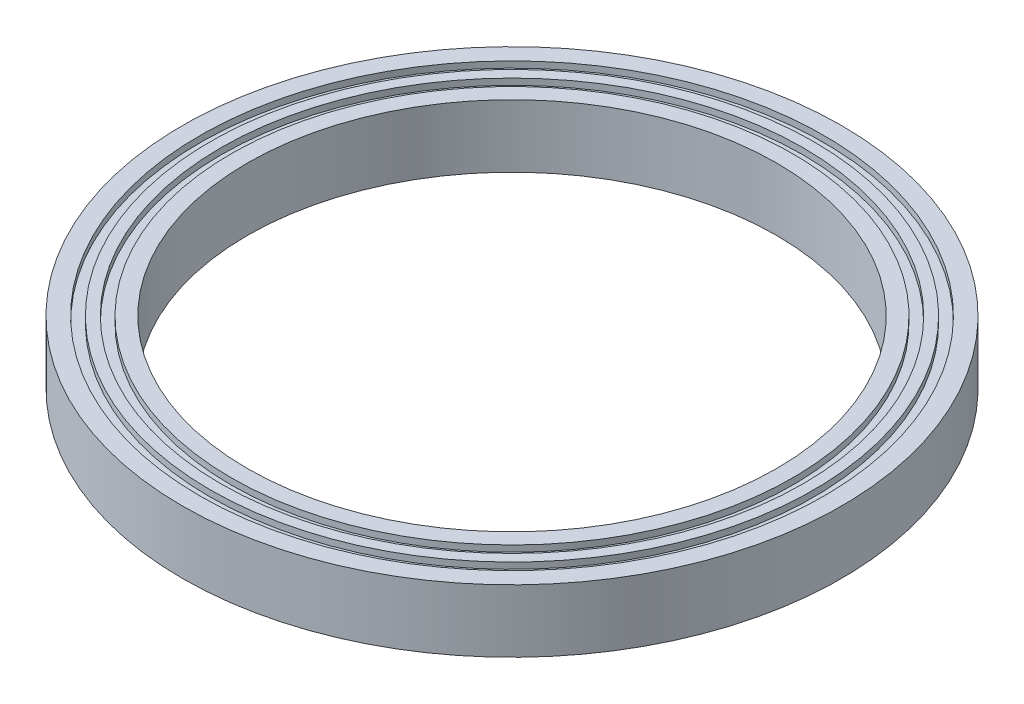
SolidWorks part; units mm, degrees
ref_plane "Front Plane" through (0, 0, 0) normal (0, 0, 1) x (1, 0, 0)
ref_plane "Top Plane" through (0, 0, 0) normal (0, 1, 0) x (1, 0, 0)
ref_plane "Right Plane" through (0, 0, 0) normal (1, 0, 0) x (0, 0, -1)
sketch "Sketch1" plane through (0, 0, 0) normal (0, 1, 0) x (1, 0, 0)
  circle A0 centre (0, 0) radius 9945
  circle A1 centre (0, 0) radius 8945
  dimension "D1" = 19890
  dimension "D2" = 17890
  dimension "D3" = 1000
extrude "Boss-Extrude1" add sketch "Sketch1" along normal blind 600
sketch "Sketch2" plane through (0, 0, 0) normal (0, 1, 0) x (1, 0, 0)
  circle A0 centre (0, 0) radius 8890
  circle A1 centre (0, 0) radius 9945
  dimension "D1" = 17780
  dimension "D2" = 19890
extrude "Boss-Extrude5" add sketch "Sketch2" along normal mid plane 2000
sketch "Sketch3" plane through (0, 1000, 0) normal (0, 1, 0) x (1, 0, 0)
  circle A0 centre (0, 0) radius 8945
  circle A1 centre (0, 0) radius 9275
  dimension "D1" = 17890
  dimension "D2" = 18550
extrude "Cut-Extrude1" cut sketch "Sketch3" against normal blind 200
sketch "Sketch4" plane through (0, 1000, 0) normal (0, 1, 0) x (1, 0, 0)
  circle A0 centre (0, 0) radius 9611.5
  circle A1 centre (0, 0) radius 9945
  dimension "D1" = 19223
  dimension "D2" = 19890
extrude "Cut-Extrude2" cut sketch "Sketch4" against normal blind 200
sketch "Sketch5" plane through (0, 0, 0) normal (0, 1, 0) x (1, 0, 0)
  circle A0 centre (0, 0) radius 10500
  circle A1 centre (0, 0) radius 9945
  dimension "D1" = 19890
extrude "Boss-Extrude6" add sketch "Sketch5" along normal mid plane 2000
sketch "Sketch6" plane through (0, 0, 0) normal (0, 1, 0) x (1, 0, 0)
  circle A0 centre (0, 0) radius 8890
  circle A1 centre (0, 0) radius 8431.0025
extrude "Boss-Extrude7" add sketch "Sketch6" along normal mid plane 2000
sketch "Sketch7" plane through (0, -1000, 0) normal (0, -1, 0) x (1, 0, 0)
  circle A1 centre (0, 0) radius 8945
  circle A2 centre (0, 0) radius 9945
  dimension "D1" = 19890
extrude "Cut-Extrude3" cut sketch "Sketch7" against normal blind 1000
